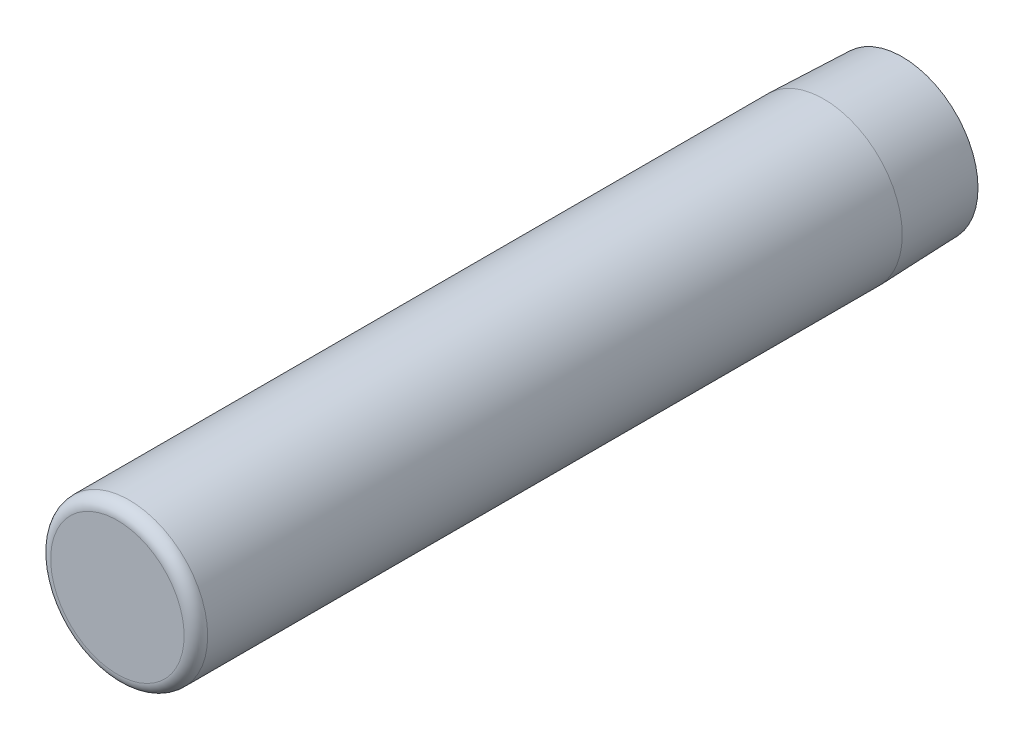
SolidWorks part; units mm, degrees
material "Acero al carbono no aleado"
ref_plane "Alzado" through (0, 0, 0) normal (0, 0, 1) x (1, 0, 0)
ref_plane "Planta" through (0, 0, 0) normal (0, 1, 0) x (1, 0, 0)
ref_plane "Vista lateral" through (0, 0, 0) normal (1, 0, 0) x (0, 0, -1)
sketch "Croquis1" plane through (0, 0, 0) normal (0, 0, 1) x (1, 0, 0)
  circle A0 centre (0, 0) radius 2
  dimension "D1" = 4
extrude "Saliente-Extruir1" add sketch "Croquis1" along normal blind 20
chamfer "Chaflán1" distance 2 angle 2 1 edges at (2, 0, 0) first distance on face at (2, 0, 20)
fillet "Redondeo1" radius 0.3 1 edges at (2, 0, 20)
